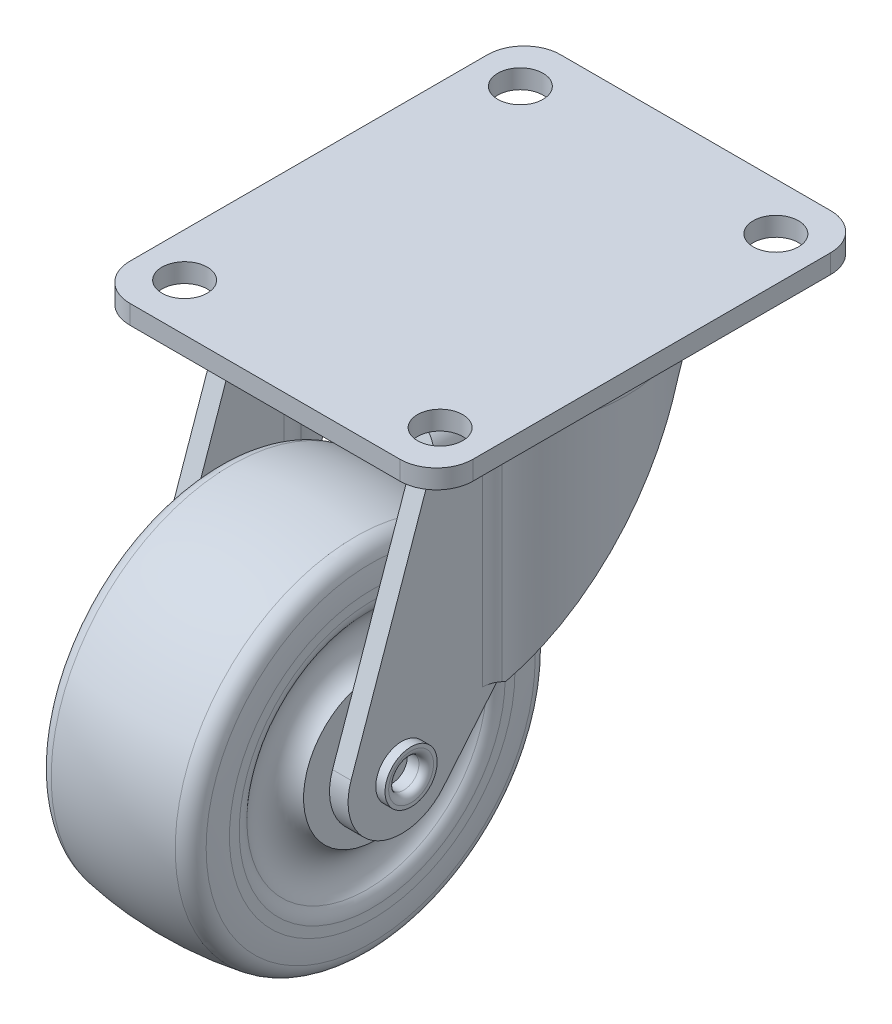
SolidWorks part; units mm, degrees
ref_plane "FRONT" through (0, 0, 0) normal (0, 0, 1) x (1, 0, 0)
ref_plane "TOP" through (0, 0, 0) normal (0, 1, 0) x (1, 0, 0)
ref_plane "RIGHT" through (0, 0, 0) normal (1, 0, 0) x (0, 0, -1)
sketch "Sketch1" plane through (0, 0, 0) normal (0, 1, 0) x (1, 0, 0)
  circle A0 centre (0, 0) radius 20
  dimension "D1" = 40
extrude "Base-Extrude" add sketch "Sketch1" against normal blind 33.02 from offset 5.588 offset against normal yes
sketch "Sketch2" plane through (0, 0, 0) normal (1, 0, 0) x (0, 0, -1)
  line L0 (-20.32, -5.588) -> (0, -5.588)
  line L1 (0, -38.608) -> (0, -5.588) construction
  line L2 (-20.32, -5.588) -> (-32.5552, -40.6746)
  line L3 (20, -5.588) -> (-20, -5.588) construction
  line L4 (-19.9388, -47.8127) -> (0, -23.8607)
  line L5 (0, 0) -> (0, -122.9181) construction
  line L6 (22, 0) -> (-22, 0) construction
  line L7 (0, 18.161) -> (0, -18.161) construction
  line L8 (0, -5.588) -> (0, -23.8607)
  line L9 (0, -23.8607) -> (10.348, -11.43) construction
  line L10 (10.348, -11.43) -> (22.032, -11.43) construction
  line L11 (20, -38.608) -> (20, -5.588) construction
  arc A0 (-32.5552, -40.6746) -> (-19.9388, -47.8127) centre (-25.6, -43.1) ccw
  circle A1 centre (-25.6, -43.1) radius 25.4 construction
  dimension "D5" = 14.732
  dimension "D7" = 68.5
  dimension "D1" = 50.8
  dimension "D4" = 51
  dimension "D2" = 20.32
  dimension "D3" = 9.652
  dimension "D6" = 11.43
extrude "Boss-Extrude1" add sketch "Sketch2" along normal mid plane 29.718
sketch "Sketch3" plane through (0, 0, 0) normal (1, 0, 0) x (0, 0, -1)
  line L0 (-19.9388, -47.8127) -> (-12.2764, -38.608) construction
  line L1 (-64.7142, -101.6) -> (10.348, -11.43)
  line L2 (38.1, -11.43) -> (38.1, -101.6)
  line L3 (-64.7142, -101.6) -> (38.1, -101.6)
  line L4 (10.348, -11.43) -> (22.032, -11.43) construction
  line L6 (10.348, -11.43) -> (38.1, -11.43)
  dimension "D1" = 38.1
  dimension "D2" = 101.6
extrude "Cut-Extrude1" cut sketch "Sketch3" against normal mid plane 76.2
fillet "Fillet1" radius 3.175 5 edges at (0, -5.588, -20) (-14.859, -5.588, 16.8535) (14.859, -5.588, 16.8535) (14.859, -22.098, 13.3869) (-14.859, -22.098, 13.3869)
fillet "Fillet2" radius 4.064 1 edges at (0, -11.43, -10.348)
shell "Shell1" thickness 2.54 removed face at (0, -34.5685, 8.9137) removed face at (0, -18.1227, 24.691) removed face at (0, -46.8773, 27.7371) removed face at (0.0625, -12.0291, -10.5342) removed face at (0, -11.43, -16.1264)
ref_plane "Plane1" through (0, 0, 25.6) normal (0, 0, 1) x (1, 0, 0)
sketch "Sketch4" plane through (-12.319, 0, 0) normal (1, 0, 0) x (0, 0, -1)
  circle A0 centre (-25.6, -43.1) radius 3.175
  arc A3 (-32.5552, -40.6746) -> (-19.9388, -47.8127) centre (-25.6, -43.1) ccw construction
  dimension "D1" = 6.35
extrude "Boss-Extrude2" add sketch "Sketch4" along normal up to next
sketch "Sketch6" plane through (0, 0, 25.6) normal (0, 0, 1) x (1, 0, 0)
  line L1 (11.303, -46.275) -> (-11.303, -46.275)
  line L2 (-12.319, -46.275) -> (12.319, -46.275) construction
  line L3 (-10.795, -61.3205) -> (-10.795, -62.658)
  line L4 (0, -43.1) -> (-22.4069, -43.1) construction
  line L5 (12.319, -43.1) -> (-12.319, -43.1) construction
  line L6 (-12.319, -43.1) -> (-14.859, -43.1) construction
  line L7 (0, -43.1) -> (0, -68.5) construction
  line L8 (-11.303, -46.275) -> (-11.303, -53.006)
  line L9 (11.303, -46.275) -> (11.303, -53.006)
  line L10 (8.89, -46.6778) -> (8.89, -54.0284) construction
  line L12 (10.795, -61.3205) -> (10.795, -62.658)
  arc A0 (-8.4953, -67.7846) -> (8.4953, -67.7846) centre (0, -17.7) ccw
  arc A1 (11.303, -53.006) -> (10.0582, -59.5316) centre (12.917, -56.6954) ccw
  arc A2 (10.795, -62.658) -> (10.5856, -65.6359) centre (-10.4796, -62.658) cw
  arc A3 (10.0582, -59.5316) -> (10.795, -61.3205) centre (8.255, -61.3205) cw
  arc A4 (10.5856, -65.6359) -> (8.4953, -67.7846) centre (8.0706, -65.2804) cw
  arc A5 (-10.5856, -65.6359) -> (-8.4953, -67.7846) centre (-8.0706, -65.2804) ccw
  arc A6 (-10.795, -62.658) -> (-10.5856, -65.6359) centre (10.4796, -62.658) ccw
  arc A7 (-10.0582, -59.5316) -> (-10.795, -61.3205) centre (-8.255, -61.3205) ccw
  arc A8 (-11.303, -53.006) -> (-10.0582, -59.5316) centre (-12.917, -56.6954) cw
  point P19 (10.795, -60.118)
  point P22 (10.2469, -67.4558)
  point P24 (0, -68.5)
  point P37 (0, -46.275)
  dimension "D4" = 21.59
  dimension "D9" = 2.54
  dimension "D6" = 50.8
  dimension "D1" = 22.606
  dimension "D2" = 19.812
  dimension "D3" = 2.413
  dimension "D5" = 7.112
  dimension "D7" = 2.54
  dimension "D8" = 10.2469
revolve "Boss-Revolve1" add sketch "Sketch6" angle 360 about L4
sketch "Sketch12" plane through (0, 0, 0) normal (1, 0, 0) x (0, 0, -1)
  circle A0 centre (-25.6, -43.1) radius 3.5736
extrude "Extrude1" add sketch "Sketch12" along normal mid plane 32.258
sketch "Sketch8" plane through (0, 0, 0) normal (1, 0, 0) x (0, 0, -1)
  line L0 (0, 25.4) -> (0, -13.5012) construction
  line L1 (10.8363, -10.9612) -> (11.43, -10.9612)
  line L2 (3.81, 0) -> (13.081, 0)
  line L3 (16.825, -5.588) -> (-10.5671, -5.588) construction
  line L4 (0, 25.4) -> (0, -13.5012)
  line L5 (15.621, -2.54) -> (15.621, -3.81)
  line L6 (0, -13.5012) -> (3.5645, -13.5012)
  line L7 (0, 25.4) -> (3.81, 25.4)
  line L8 (15.875, -3.81) -> (15.621, -3.81)
  line L9 (0, 0) -> (0, 58.0131) construction
  line L10 (3.81, 25.4) -> (3.81, 0)
  line L11 (15.875, -3.81) -> (15.875, -5.588)
  line L12 (22, 0) -> (-22, 0) construction
  line L13 (0, -38.608) -> (0, -8.763) construction
  line L14 (15.875, -5.588) -> (6.35, -5.588)
  line L15 (6.35, -5.588) -> (6.35, -10.9612)
  line L16 (11.43, -10.9612) -> (11.43, -13.5012)
  line L20 (6.35, -10.9612) -> (4.1581, -10.9612)
  arc A0 (15.621, -2.54) -> (13.081, 0) centre (13.081, -2.54) ccw
  arc A1 (3.5645, -13.5012) -> (11.43, -13.5012) centre (7.4972, -4.826) ccw
  arc A11 (4.1581, -10.9612) -> (10.8363, -10.9612) centre (7.4972, -4.826) ccw
  dimension "D6" = 39.751
  dimension "D8" = 9.525
  dimension "D2" = 2.54
  dimension "D3" = 0.254
  dimension "D4" = 25.4
  dimension "D5" = 7.62
  dimension "D7" = 22.86
  dimension "D9" = 5.3732
  dimension "D11" = 12.7
  dimension "D12" = 31.75
  dimension "D13" = 1.778
  dimension "D10" = 2.54
revolve "Boss-Revolve2" [suppressed] add sketch "Sketch8" angle 360 about L9
chamfer "Chamfer1" [suppressed] distance 1.016 angle 45
sketch "Sketch9" [suppressed] plane through (0, 25.4, 0) normal (0, 1, 0) x (-1, 0, 0)
  line L1 (0, 7.3323) -> (-6.35, 3.6662)
  line L2 (-6.35, 3.6662) -> (-6.35, -3.6662)
  line L3 (-6.35, -3.6662) -> (0, -7.3323)
  line L4 (0, -7.3323) -> (6.35, -3.6662)
  line L5 (6.35, -3.6662) -> (6.35, 3.6662)
  line L6 (6.35, 3.6662) -> (0, 7.3323)
  circle A0 centre (0, 0) radius 6.35 construction
  circle A1 centre (0, 0) radius 3.81 construction
  circle A2 centre (0, 0) radius 3.81
  dimension "D1" = 12.7
extrude "Boss-Extrude3" [suppressed] add sketch "Sketch9" against normal blind 7.7978 from offset 1.27 offset against normal yes
sketch "Sketch10" [suppressed] plane through (0, 6.8128, 0.1695) normal (1, 0, 0) x (0, 0, -1)
  line L0 (0.1695, 0) -> (0.1695, 22.4951) construction
  line L3 (-8.6869, 9.5194) -> (-5.6389, 9.5194)
  line L5 (-8.6869, 17.3172) -> (-5.6389, 17.3172)
  line L7 (-7.1629, 16.4373) -> (-7.1629, 10.3992)
  line L8 (-8.6869, 17.3172) -> (-8.6869, 9.5194)
  line L9 (-5.6389, 17.3172) -> (-7.1629, 16.4373)
  line L10 (-5.6389, 9.5194) -> (-7.1629, 10.3992)
  line L11 (0.1695, 12.5775) -> (0.1695, -26.2032) construction
  line L12 (-7.1629, 9.5194) -> (-7.1629, 17.3172) construction
  line L13 (-7.1629, 13.4183) -> (-8.6869, 13.4183) construction
  line L14 (-7.1629, 17.3172) -> (-3.4967, 17.3172) construction
  dimension "D1" = 0.8799
  dimension "D2" = 1.524
  dimension "D3" = 1.524
revolve "Cut-Revolve1" [suppressed] cut sketch "Sketch10" angle 360 about L0
sketch "Sketch15" plane through (0, -5.588, 0) normal (0, 1, 0) x (1, 0, 0)
  circle A0 centre (0, 0) radius 15
  dimension "D1" = 30
extrude "Boss-Extrude4" add sketch "Sketch15" along normal blind 0.703
sketch "Sketch16" plane through (0, -4.885, 0) normal (0, 1, 0) x (1, 0, 0)
  line L1 (-23.5, -29.5) -> (23.5, -29.5)
  line L2 (-23.5, -29.5) -> (-23.5, 29.5)
  line L3 (-23.5, 29.5) -> (23.5, 29.5)
  line L4 (23.5, -29.5) -> (23.5, 29.5)
  line L5 (-23.5, -29.5) -> (23.5, 29.5) construction
  line L6 (-23.5, 29.5) -> (23.5, -29.5) construction
  point P0 (0, 0)
  dimension "D1" = 47
  dimension "D2" = 59
extrude "Boss-Extrude5" add sketch "Sketch16" along normal blind 2.6
sketch "Sketch17" plane through (0, -2.285, 0) normal (0, 1, 0) x (1, 0, 0)
  line L0 (0, -29.5) -> (0, 29.5) construction
  line L1 (23.5, 29.5) -> (-23.5, 29.5) construction
  line L2 (-23.5, 0) -> (23.5, 0) construction
  line L3 (23.5, -29.5) -> (23.5, 29.5) construction
  circle A0 centre (-17.5, 23) radius 3.1
  circle A1 centre (17.5, 23) radius 3.1
  circle A2 centre (17.5, -23) radius 3.1
  circle A3 centre (-17.5, -23) radius 3.1
  point P6 (0, 0)
  point P11 (0, 0)
  dimension "D3" = 6.2
  dimension "D1" = 35
  dimension "D2" = 46
extrude "Cut-Extrude2" cut sketch "Sketch17" against normal blind 2.6
fillet "Fillet3" radius 5 4 edges at (-23.5, -3.585, -29.5) (-23.5, -3.585, 29.5) (23.5, -3.585, 29.5) (23.5, -3.585, -29.5)
sketch "Sketch18" plane through (16.129, 0, 0) normal (1, 0, 0) x (0, 0, -1)
  circle A2 centre (-25.6, -43.1) radius 2.0736
  circle A3 centre (-25.6, -43.1) radius 2.0736
  dimension "D1" = 1.5
extrude "Cut-Extrude3" cut sketch "Sketch18" against normal blind 2.6
fillet "Fillet4" radius 1 1 edges at (16.129, -43.1, 23.5264)
fillet "Fillet5" radius 1 1 edges at (-16.129, -43.1, 22.0264)
fillet "Fillet6" radius 10 1 edges at (-11.303, -43.1, 15.694)
sketch "Sketch13" [suppressed] plane through (14.859, 0, 0) normal (1, 0, 0) x (0, 0, -1)
  line L0 (-51, -43.1) -> (29.5, -43.1) construction
  line L1 (20, -11.43) -> (20, -43.1) construction
  line L2 (-25.6, -67.7846) -> (-25.6, -2.285) construction
  line L3 (0, -2.285) -> (-25.6, -2.285) construction
  line L5 (-24.5, -2.285) -> (24.5, -2.285) construction
  line L6 (29.5, -2.285) -> (29.5, -43.1) construction
  circle A0 centre (-25.6, -43.1) radius 25.4 construction
  circle A1 centre (-25.6, -43.1) radius 24.6846 construction
  circle A2 centre (-25.6, -43.1) radius 24.6846 construction
  point P11 (0, -2.285)
  dimension "D1" = 71
  dimension "D2" = 65.4996
  dimension "D3" = 80.5
  dimension "D4" = 9.5
sketch "Sketch19" plane through (-23.5, 0, 0) normal (-1, 0, 0) x (0, 0, 1)
  line L0 (29.5, -2.285) -> (24.5, -2.285) construction
  line L1 (24.5, -2.285) -> (24.5, -4.885) construction
  line L2 (24.5, -4.885) -> (29.5, -4.885) construction
  line L3 (29.5, -4.885) -> (29.5, -2.285) construction
  line L4 (24.5, -2.285) -> (-24.5, -2.285)
  line L5 (-24.5, -2.285) -> (-24.5, -4.885)
  line L6 (-24.5, -4.885) -> (24.5, -4.885)
  line L7 (24.5, -4.885) -> (24.5, -2.285)
  line L8 (24.5, -2.285) -> (-24.5, -2.285)
  line L9 (-24.5, -2.285) -> (-24.5, -4.885)
  line L10 (-24.5, -4.885) -> (24.5, -4.885)
  line L11 (24.5, -4.885) -> (24.5, -2.285)
  line L12 (-24.5, -2.285) -> (-29.5, -2.285) construction
  line L13 (-29.5, -2.285) -> (-29.5, -4.885) construction
  line L14 (-29.5, -4.885) -> (-24.5, -4.885) construction
  line L15 (-24.5, -4.885) -> (-24.5, -2.285) construction
  line L16 (29.5, -2.285) -> (24.5, -2.285)
  line L17 (24.5, -2.285) -> (24.5, -4.885)
  line L18 (24.5, -4.885) -> (29.5, -4.885)
  line L19 (29.5, -4.885) -> (29.5, -2.285)
  line L20 (-24.5, -2.285) -> (-29.5, -2.285)
  line L21 (-29.5, -2.285) -> (-29.5, -4.885)
  line L22 (-29.5, -4.885) -> (-24.5, -4.885)
  line L23 (-24.5, -4.885) -> (-24.5, -2.285)
  line L25 (-29.5, -2.285) -> (51, -2.285)
  line L26 (-29.5, -2.285) -> (-29.5, -68.5)
  line L27 (-29.5, -68.5) -> (51, -68.5)
  line L28 (51, -2.285) -> (51, -68.5)
  circle A0 centre (25.6, -43.1) radius 25.4 construction
  circle A1 centre (25.6, -43.1) radius 25.4
  dimension "D1" = 0
